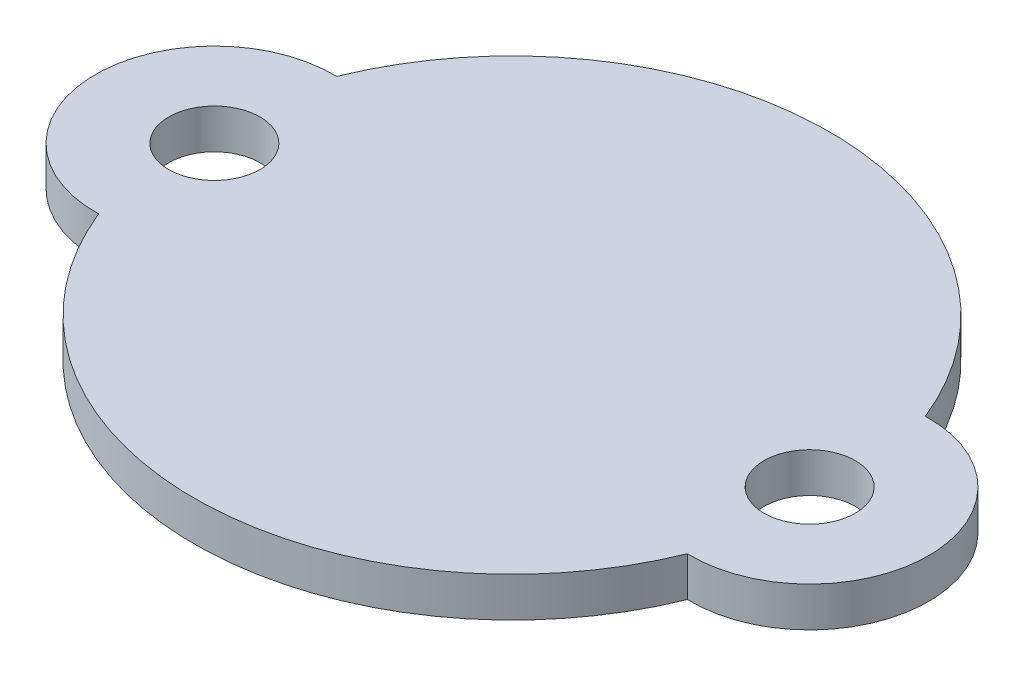
SolidWorks part; units mm, degrees
ref_plane "Front Plane" through (0, 0, 0) normal (0, 0, 1) x (1, 0, 0)
ref_plane "Top Plane" through (0, 0, 0) normal (0, 1, 0) x (1, 0, 0)
ref_plane "Right Plane" through (0, 0, 0) normal (1, 0, 0) x (0, 0, -1)
sketch "Sketch1" plane through (0, 0, 0) normal (0, 1, 0) x (1, 0, 0)
  circle A0 centre (0, 0) radius 8
  circle A2 centre (7.5, 0) radius 3
  circle A3 centre (-7.5, 0) radius 3
  circle A4 centre (7.5, 0) radius 1.15
  circle A5 centre (-7.5, 0) radius 1.15
  circle A6 centre (0, 0) radius 7.5 construction
  point P10 (7.5, 0)
  point P11 (0, 0)
  point P12 (0, 0)
  point P13 (-7.5, 0)
  dimension "D1" = 16
  dimension "D2" = 15
  dimension "D3" = 6
  dimension "D5" = 2.3
extrude "Boss-Extrude1" add sketch "Sketch1" along normal blind 1 contours A3 A0 A2 | A4 A0 A2 | A4 A0 A2 | A5 A0 A3 | A5 A0 A3 region at (6.1874, 0, 0) region at (8.9956, 0, 0) region at (0, 0, 0) region at (-6.1874, 0, 0) region at (-8.9956, 0, 0)
